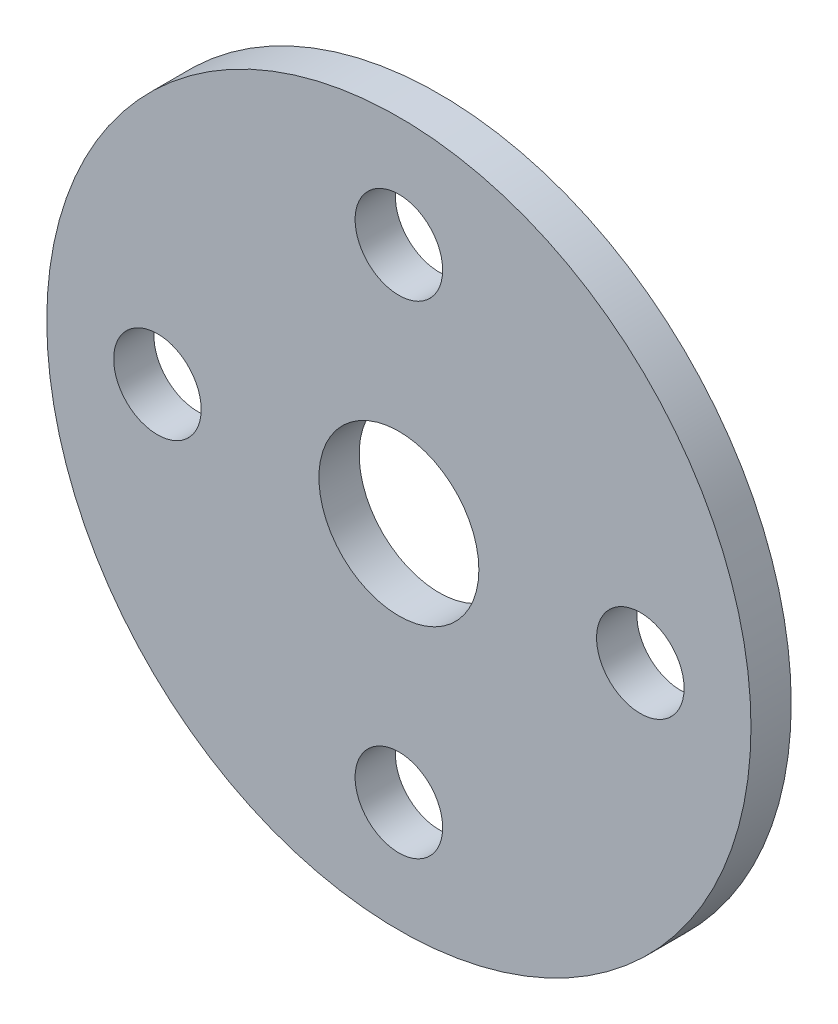
SolidWorks part; units mm, degrees
ref_plane "Front Plane" through (0, 0, 0) normal (0, 0, 1) x (1, 0, 0)
ref_plane "Top Plane" through (0, 0, 0) normal (0, 1, 0) x (1, 0, 0)
ref_plane "Right Plane" through (0, 0, 0) normal (1, 0, 0) x (0, 0, -1)
sketch "Sketch1" plane through (0, 0, 0) normal (0, 0, 1) x (1, 0, 0)
  circle A0 centre (0, 0) radius 17.5
  circle A2 centre (12, 0) radius 2.175
  circle A3 centre (0, 12) radius 2.175
  circle A4 centre (-12, 0) radius 2.175
  circle A5 centre (0, -12) radius 2.175
  circle A6 centre (0, 0) radius 3.975
  dimension "D1" = 4.35
  dimension "D2" = 4.35
  dimension "D3" = 4.35
  dimension "D4" = 4.35
  dimension "D5" = 7.95
  dimension "D6" = 12
  dimension "D7" = 12
  dimension "D8" = 12
extrude "Boss-Extrude1" add sketch "Sketch1" along normal blind 2
